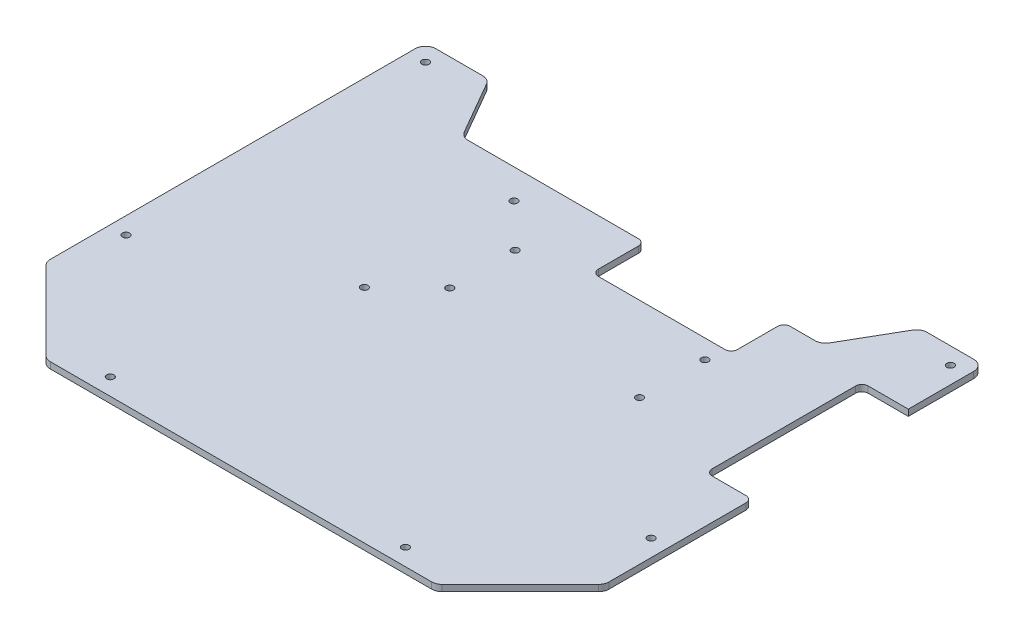
SolidWorks part; units mm, degrees
material "Acier non allié"
ref_plane "Front" through (0, 0, 0) normal (0, 0, 1) x (1, 0, 0)
ref_plane "Top" through (0, 0, 0) normal (0, 1, 0) x (1, 0, 0)
ref_plane "Right" through (0, 0, 0) normal (1, 0, 0) x (0, 0, -1)
sketch "Esquisse1" plane through (0, 0, 0) normal (0, 1, 0) x (1, 0, 0)
  line L0 (0, 0) -> (0, 190) construction
  line L1 (-92.5, 0) -> (92.5, 0)
  line L2 (92.5, 0) -> (132.5, 40)
  line L3 (132.5, 40) -> (132.5, 220)
  line L4 (132.5, 220) -> (102.5, 220)
  line L5 (102.5, 220) -> (85.1795, 190)
  line L6 (85.1795, 190) -> (-85.1795, 190)
  line L7 (-102.5, 220) -> (-85.1795, 190)
  line L8 (-132.5, 220) -> (-102.5, 220)
  line L9 (-132.5, 40) -> (-132.5, 220)
  line L10 (-92.5, 0) -> (-132.5, 40)
  dimension "D1" = 132.5
  dimension "D2" = 220
  dimension "D3" = 60
  dimension "D4" = 30
  dimension "D5" = 40
  dimension "D6" = 40
  dimension "D7" = 30
extrude "Boss.-Extru.1" add sketch "Esquisse1" along normal blind 3
fillet "Congé1" radius 5 10 edges at (92.5, 1.5, 0) (132.5, 1.5, -40) (132.5, 1.5, -220) (102.5, 1.5, -220) (85.1795, 1.5, -190) (-85.1795, 1.5, -190) (-102.5, 1.5, -220) (-132.5, 1.5, -220) (-92.5, 1.5, 0) (-132.5, 1.5, -40)
sketch "Esquisse2" plane through (0, 3, 0) normal (0, 1, 0) x (1, 0, 0)
  line L0 (0, 0) -> (0, 294.1173) construction
  line L2 (-90.4289, 0) -> (90.4289, 0) construction
  circle A0 centre (70, 8) radius 1
  circle A1 centre (124.5, 70) radius 1
  circle A2 centre (124.5, 212) radius 1
  circle A3 centre (-124.5, 212) radius 1
  circle A4 centre (-124.5, 70) radius 1
  circle A5 centre (-70, 8) radius 1
  dimension "D2" = 2
  dimension "D6" = 2
  dimension "D9" = 2
  dimension "D1" = 70
  dimension "D3" = 8
  dimension "D4" = 124.5
  dimension "D5" = 70
  dimension "D7" = 124.5
  dimension "D8" = 212
extrude "Enlèv. mat.-Extru.1" cut sketch "Esquisse2" against normal blind 3
hole_wizard "Dégagement M31" positions "Esquisse3" profile "Esquisse4" hole size "M3" standard "ISO" end condition through all
sketch "Esquisse3" plane through (0, 3, 0) normal (0, 1, 0) x (1, 0, 0)
  point P0 (70, 8)
  point P3 (-70, 8)
  point P6 (-124.5, 70)
  point P9 (-124.5, 212)
  point P12 (124.5, 212)
  point P15 (124.5, 70)
sketch "Esquisse4" plane through (70, 3, -8) normal (1, 0, 0) x (0, 0, 1)
  line L0 (0, 0) -> (0, 3)
  line L1 (0, 3) -> (1.7, 3)
  line L2 (1.7, 3) -> (1.7, 0)
  line L5 (1.7, 0) -> (0, 0)
  line L11 (0, -6.35) -> (0, 107.95) construction
  dimension "Diamètre du perçage jusqu'au prochain" = 3.4
  dimension "Profondeur du perçage jusqu'au prochain" = 3
sketch "Esquisse5" plane through (0, 3, 0) normal (0, 1, 0) x (1, 0, 0)
  line L0 (82.2927, 190) -> (-82.2927, 190) construction
  line L1 (67.5, 190) -> (1.5, 190)
  line L2 (67.5, 190) -> (67.5, 165)
  line L3 (67.5, 165) -> (1.5, 165)
  line L4 (1.5, 190) -> (1.5, 165)
  line L5 (132.5, 42.0711) -> (132.5, 215) construction
  line L6 (132.5, 184) -> (110.5, 184)
  line L7 (132.5, 184) -> (132.5, 110)
  line L8 (132.5, 110) -> (110.5, 110)
  line L9 (110.5, 184) -> (110.5, 110)
  line L10 (127.5, 220) -> (105.3868, 220) construction
  dimension "D1" = 25
  dimension "D2" = 65
  dimension "D3" = 131
  dimension "D4" = 36
  dimension "D5" = 110
  dimension "D6" = 22
extrude "Enlèv. mat.-Extru.2" cut sketch "Esquisse5" against normal through all
fillet "Congé2" radius 3 7 edges at (132.5, 1.5, -110) (110.5, 1.5, -110) (110.5, 1.5, -184) (67.5, 1.5, -190) (67.5, 1.5, -165) (1.5, 1.5, -165) (1.5, 1.5, -190)
sketch "Esquisse6" plane through (0, 3, 0) normal (0, 1, 0) x (1, 0, 0)
  line L0 (110.5, 140.5) -> (-167.6757, 140.5) construction
  line L1 (110.5, 181) -> (110.5, 113) construction
  line L2 (-90.4289, 0) -> (90.4289, 0) construction
  line L3 (110.5, 181) -> (110.5, 113) construction
  circle A0 centre (64, 156) radius 1
  circle A1 centre (-26, 156) radius 1
  circle A2 centre (-46.5, 176) radius 1
  circle A3 centre (64, 125) radius 1
  circle A4 centre (-26, 125) radius 1
  circle A5 centre (-46.5, 105) radius 1
  dimension "D4" = 2
  dimension "D6" = 2
  dimension "D10" = 2
  dimension "D1" = 140.5
  dimension "D2" = 46.5
  dimension "D3" = 15.5
  dimension "D5" = 136.5
  dimension "D7" = 15.5
  dimension "D8" = 35.5
  dimension "D9" = 157
extrude "Enlèv. mat.-Extru.3" cut sketch "Esquisse6" against normal through all
hole_wizard "Dégagement M32" positions "Esquisse7" profile "Esquisse8" hole size "M3" standard "ISO"
sketch "Esquisse7" plane through (0, 3, 0) normal (0, 1, 0) x (1, 0, 0)
  point P0 (-46.5, 105)
  point P3 (-26, 125)
  point P6 (-26, 156)
  point P9 (-46.5, 176)
  point P12 (64, 156)
  point P15 (64, 125)
sketch "Esquisse8" plane through (-46.5, 3, -105) normal (1, 0, 0) x (0, 0, 1)
  line L0 (0, 0) -> (0, 11.0215)
  line L1 (0, 11.0215) -> (1.7, 10)
  line L2 (1.7, 10) -> (1.7, 0)
  line L5 (1.7, 0) -> (0, 0)
  line L10 (0, 11.0215) -> (-1.7, 10) construction
  line L11 (0, -6.35) -> (0, 107.95) construction
  dimension "Diamètre du perçage" = 3.4
  dimension "Profondeur du perçage" = 10
  dimension "Angle de pointe" = 118
equation "\"WIDTH\"= 300mm'Total width of the robot"
equation "\"LENGTH\"= 220mm'Total length of the robot"
equation "\"CUT_DEPTH\"= 45mm'Depth of the cut on the edges of the plate"
equation "\"Plate_th\"= 3mm'Thickness of the plate"
equation "\"D1\"= \"Plate_th\""
